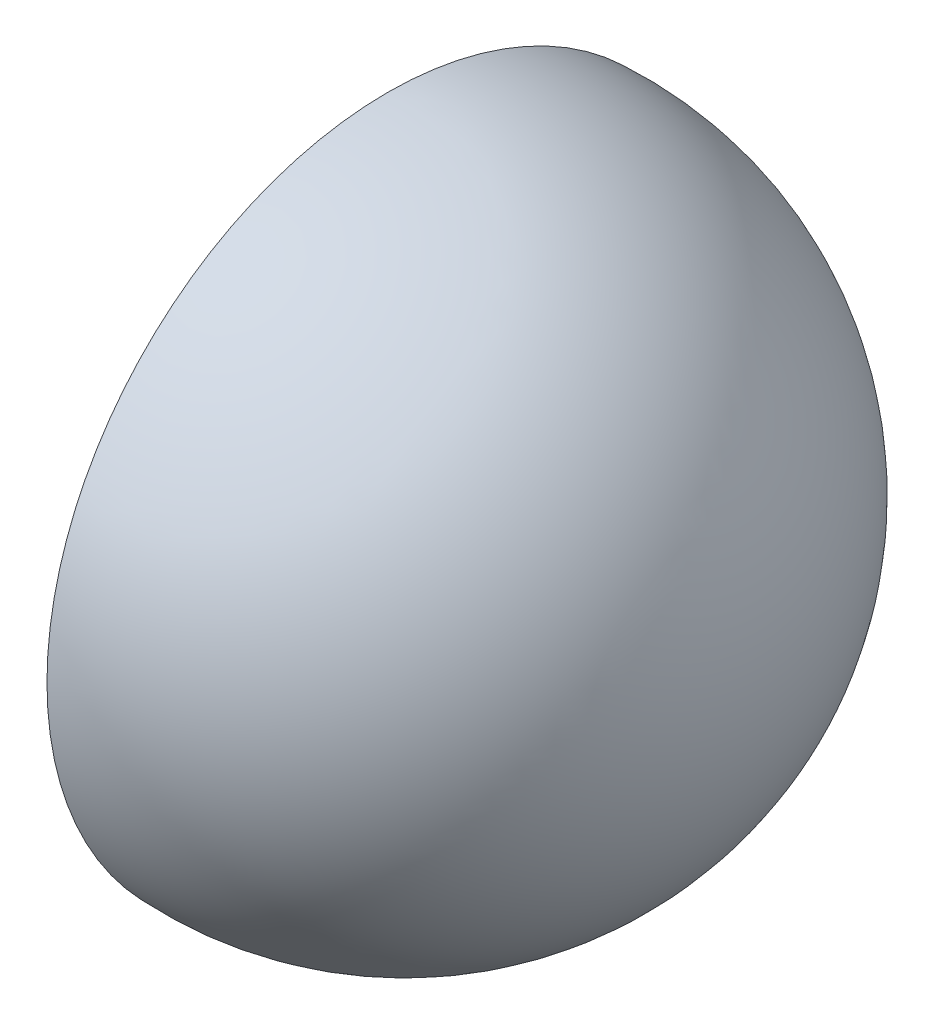
SolidWorks part; units mm, degrees
ref_plane "Front Plane" through (0, 0, 0) normal (0, 0, 1) x (1, 0, 0)
ref_plane "Top Plane" through (0, 0, 0) normal (0, 1, 0) x (1, 0, 0)
ref_plane "Right Plane" through (0, 0, 0) normal (1, 0, 0) x (0, 0, -1)
sketch "Sketch1" plane through (0, 0, 0) normal (0, 0, 1) x (1, 0, 0)
  line L0 (0, 100) -> (0, 0) construction
  line L3 (-5, 99.8749) -> (-5, 97.3717) construction
  line L4 (-5, 99.8749) -> (-5, 97.3717)
  line L6 (-5, 0) -> (100, 0) construction
  line L7 (95, 0) -> (100, 0)
  line L8 (5, 99.8749) -> (5, 0) construction
  line L10 (-5, 94.8683) -> (-5, 0) construction
  line L14 (-5, 97.3717) -> (5, 97.3717)
  line L15 (5, 97.3717) -> (5, 94.8683)
  arc A4 (95, 0) -> (5, 94.8683) centre (0, 0) ccw
  arc A5 (100, 0) -> (-5, 99.8749) centre (0, 0) ccw
  arc A6 (97.5, 0) -> (-5, 97.3717) centre (0, 0) ccw construction
  point P13 (5, 97.3717)
  dimension "D1" = 100
  dimension "D2" = 95
  dimension "D5" = 97.5
  dimension "D3" = 5
  dimension "D4" = 5
  dimension "D6" = 10
revolve "Revolve4" add sketch "Sketch1" angle 360 about L6
thread "Thread2" pitch 2 method cut profile "Thread Profile2" start angle 0, offset 0, length 0, pitch 2, diameter 194.7434
ref_plane "Plane2" through (-5, 0, -97.3717) normal (0, -1, 0) x (0, 0, -1)
sketch "Thread Profile2" plane through (-5, 0, -97.3717) normal (0, -1, 0) x (0, 0, -1)
  line L0 (0, 0) -> (0, 2) construction
  line L1 (0, 0) -> (1.0825, 0.625)
  line L2 (1.0825, 0.625) -> (1.0825, 0.875)
  line L3 (1.0825, 0.875) -> (0, 1.5)
  line L4 (1.0825, 0.75) -> (0, 0.75) construction
  line L11 (0, 0) -> (0, 1.5)
  point P2 (0, 0)
  dimension "Pitch" = 2
  dimension "Profile_Angle" = 60
  dimension "Profile_Land" = 0.25
  dimension "Profile_Height" = 1.0825
